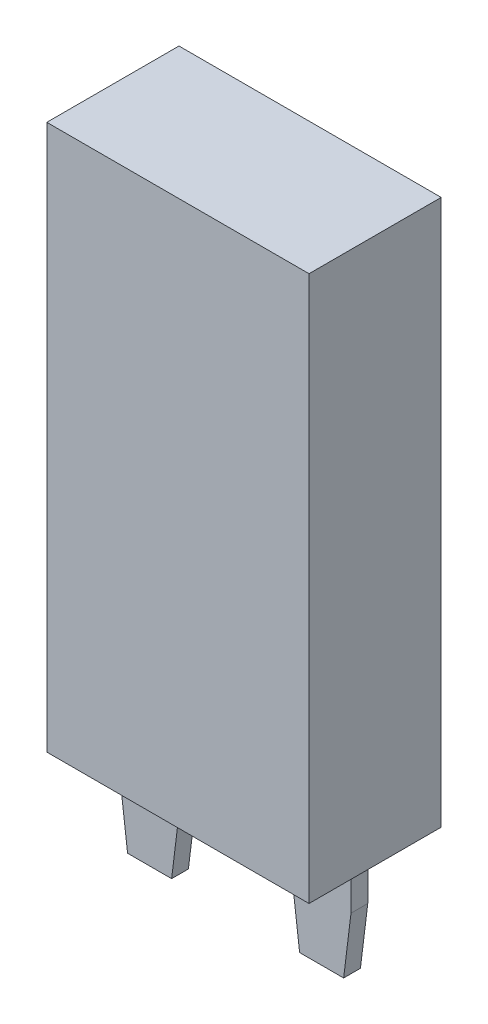
SolidWorks part; units mm, degrees
ref_plane "Front Plane" through (0, 0, 0) normal (0, 0, 1) x (1, 0, 0)
ref_plane "Top Plane" through (0, 0, 0) normal (0, 1, 0) x (1, 0, 0)
ref_plane "Right Plane" through (0, 0, 0) normal (1, 0, 0) x (0, 0, -1)
sketch "Sketch1" plane through (0, 0, 0) normal (0, 0, 1) x (1, 0, 0)
  line L1 (-6.25, 13) -> (6.25, 13)
  line L2 (-6.25, 13) -> (-6.25, -13)
  line L3 (-6.25, -13) -> (6.25, -13)
  line L4 (6.25, 13) -> (6.25, -13)
  line L5 (-6.25, 13) -> (6.25, -13) construction
  line L6 (-6.25, -13) -> (6.25, 13) construction
  point P0 (0, 0)
  dimension "D1" = 26
  dimension "D2" = 12.5
extrude "Boss-Extrude1" add sketch "Sketch1" along normal mid plane 6.3
sketch "Sketch2" plane through (0, -13, 0) normal (0, -1, 0) x (1, 0, 0)
  line L0 (0, 3.9068) -> (0, -3.8663) construction
  line L1 (2.7, 0.4) -> (2.7, -0.4)
  line L2 (-5.5, 0.4) -> (-2.7, 0.4)
  line L3 (-5.5, 0.4) -> (-5.5, -0.4)
  line L4 (-5.5, -0.4) -> (-2.7, -0.4)
  line L5 (-2.7, 0.4) -> (-2.7, -0.4)
  line L6 (5.5, -0.4) -> (2.7, -0.4)
  line L7 (5.5, 0.4) -> (5.5, -0.4)
  line L8 (5.5, 0.4) -> (2.7, 0.4)
  point P7 (-2.7, 0)
  dimension "D1" = 2.8
  dimension "D2" = 0.8
  dimension "D3" = 11
extrude "Boss-Extrude2" add sketch "Sketch2" along normal blind 5
chamfer "Chamfer1" distance 0.35 angle 83 4 edges at (5.5, -18, 0) (2.7, -18, 0) (-2.7, -18, 0) (-5.5, -18, 0) first distance on face at (4.1, -18, 0) first distance on face at (-4.1, -18, 0)
